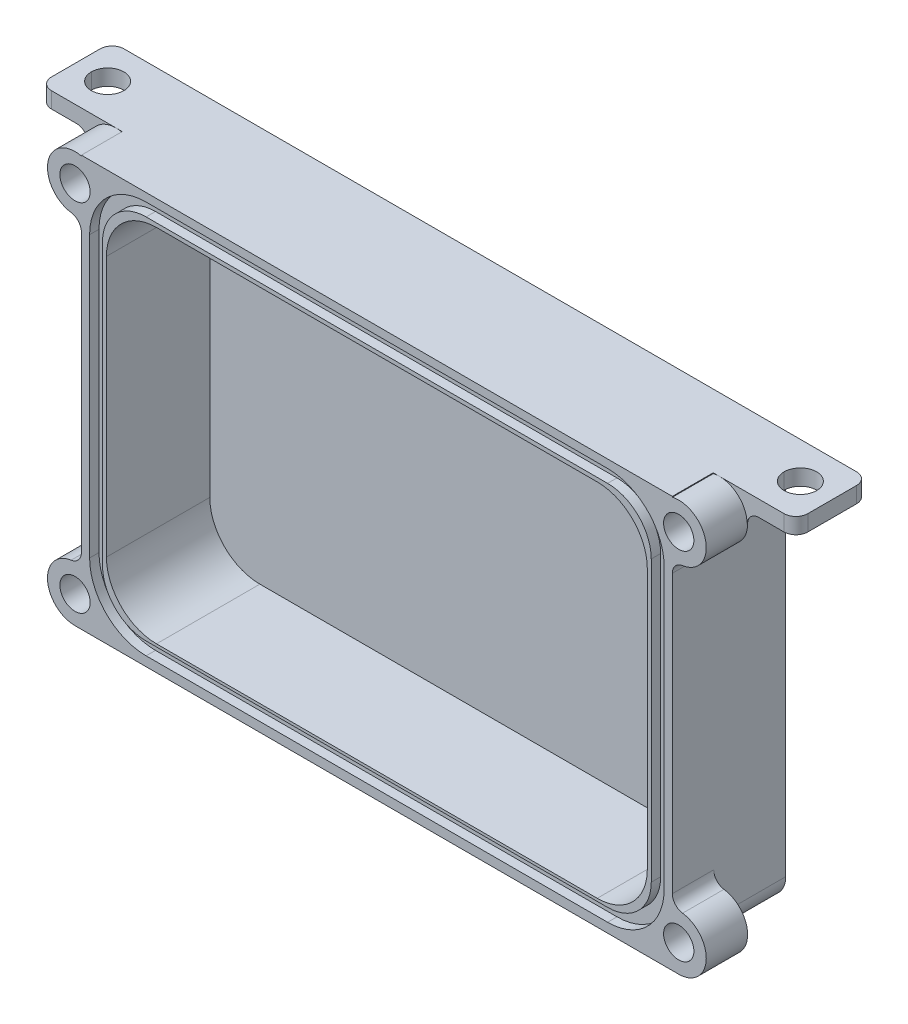
SolidWorks part; units mm, degrees
note: The reader was unsure of these and kept them because the rebuilt part matched: shared geometry of "Sketch6<4>".
material "ABS PC"
ref_plane "X-Y Datum" through (0, 0, 0) normal (0, 0, 1) x (1, 0, 0)
ref_plane "X-Z Datum" through (0, 0, 0) normal (0, 1, 0) x (1, 0, 0)
ref_plane "Y-Z Datum" through (0, 0, 0) normal (1, 0, 0) x (0, 0, -1)
sketch "Sketch2" plane through (0, 0, 0) normal (0, 0, 1) x (1, 0, 0)
  line L1 (-54, 36) -> (54, 36)
  line L2 (-54, 36) -> (-54, -36)
  line L3 (-54, -36) -> (54, -36)
  line L4 (54, 36) -> (54, -36)
  line L5 (-54, 36) -> (54, -36) construction
  line L6 (-54, -36) -> (54, 36) construction
  point P0 (0, 0)
  dimension "D1" = 72
  dimension "D2" = 108
extrude "Boss-Extrude1" add sketch "Sketch2" along normal blind 20.64
shell "Shell1" thickness 5
sketch "Sketch3" plane through (0, 0, -5) normal (0, 0, -1) x (-1, 0, 0)
  line L4 (59, 41) -> (-59, 41)
  line L5 (-59, 41) -> (-59, -41)
  line L6 (-59, -41) -> (59, -41)
  line L7 (59, -41) -> (59, 41)
  line L8 (59, 41) -> (-59, 41)
  line L9 (-59, 41) -> (-59, -41)
  line L10 (-59, -41) -> (59, -41)
  line L11 (59, -41) -> (59, 41)
  dimension "D1" = 0
extrude "Cut-Extrude1" cut sketch "Sketch3" against normal blind 3
fillet "Fillet1" radius 10 4 edges at (54, -36, 10.32) (-54, -36, 10.32) (54, 36, 10.32) (-54, 36, 10.32)
sketch "Sketch13" plane through (0, 41, 0) normal (0, 1, 0) x (1, 0, 0)
  line L1 (-59, 2) -> (-75.51, 2)
  line L2 (-59, 2) -> (-59, -12.478)
  line L3 (-59, -12.478) -> (-75.51, -12.478)
  line L4 (-75.51, 2) -> (-75.51, -12.478)
  line L5 (-59, 2) -> (59, 2) construction
  line L6 (-75.51, -5.239) -> (-59, -5.239) construction
  line L7 (-59, -20.64) -> (-59, 2) construction
  circle A0 centre (-69.16, -5.239) radius 3.25
  point P8 (-63.0691, -9.32)
  point P13 (-67.383, -9.32)
  point P16 (-70.43, -4.0285)
  dimension "D1" = 6.5
  dimension "D2" = 10.16
  dimension "D3" = 16.51
  dimension "D4" = 7.239
  dimension "D5" = 14.478
extrude "Boss-Extrude4" add sketch "Sketch13" against normal blind 3.175 contours A0 | L1 L4 L3 L2
mirror "Mirror4" about plane through (0, 0, 0) normal (1, 0, 0) of "Boss-Extrude4"
sketch "Sketch6" plane through (0, 0, 20.64) normal (0, 0, 1) x (1, 0, 0)
  line L0 (-59, -41) -> (59, -41) construction
  line L1 (60.27, -41) -> (59, -41)
  line L3 (12.452, 0) -> (-12.452, 0) construction
  line L6 (0, -12.452) -> (0, 12.452) construction
  line L7 (59, -41) -> (59, 41) construction
  line L8 (59, -41) -> (59, -40.8514)
  arc A2 (60.27, -41) -> (59, -40.8514) centre (60.27, -35.5) ccw
  circle A3 centre (60.27, -35.5) radius 3.025
  circle A6 centre (60.27, 35.5) radius 5.5
  circle A7 centre (60.27, 35.5) radius 3.025
  circle A8 centre (-60.27, -35.5) radius 3.025
  circle A9 centre (-60.27, -35.5) radius 5.5
  circle A10 centre (-60.27, 35.5) radius 3.025
  circle A11 centre (-60.27, 35.5) radius 5.5
  line M16 (59, -41) -> (59, 41)
  line M20 (-59, 41) -> (-59, -41)
  dimension "D1" = 11
  dimension "D2" = 6.05
  dimension "D3" = 1.27
extrude "Boss-Extrude2" add sketch "Sketch6" against normal blind 8.255
extrude "Cut-Extrude4" cut sketch "Sketch6<4>" against normal blind 6.35 contours A7 M16 | A7 M16 | A3 M16 | A3 M16 | A8 M20 | A8 M20 | A10 M20 | A10 M20
sketch "Sketch6<4>" plane through (0, 0, 20.64) normal (0, 0, 1) x (1, 0, 0) same geometry as "Sketch6"
mirror "Mirror5" about plane through (0, 0, 0) normal (1, 0, 0) of "Cut-Extrude4", "Boss-Extrude2"
sketch "Sketch5" plane through (0, 0, 20.64) normal (0, 0, 1) x (1, 0, 0)
  line L0 (-46.0711, 38.0711) -> (46.0711, 38.0711) construction
  line L5 (56.0711, 28.0711) -> (56.0711, -27.825) construction
  line L6 (46.0711, -37.825) -> (-46.0711, -37.825) construction
  line L7 (-56.0711, -27.825) -> (-56.0711, 28.0711) construction
  line L8 (46.0711, -39.11) -> (-46.0711, -39.11)
  line L9 (-57.3561, -27.825) -> (-57.3561, 28.0711)
  line L10 (-46.0711, 39.3561) -> (46.0711, 39.3561)
  line L11 (57.3561, 28.0711) -> (57.3561, -27.825)
  line L12 (46.0711, -36.54) -> (-46.0711, -36.54)
  line L13 (-54.7861, -27.825) -> (-54.7861, 28.0711)
  line L14 (-46.0711, 36.7861) -> (46.0711, 36.7861)
  line L15 (54.7861, 28.0711) -> (54.7861, -27.825)
  line L16 (-44, -36) -> (44, -36) construction
  arc A0 (-49, 41) -> (-59, 31) centre (-49, 31) ccw construction
  arc A1 (59, 31) -> (49, 41) centre (49, 31) ccw construction
  arc A2 (56.0711, -27.825) -> (46.0711, -37.825) centre (46.0711, -27.825) cw construction
  arc A3 (46.0711, 38.0711) -> (56.0711, 28.0711) centre (46.0711, 28.0711) cw construction
  arc A4 (-46.0711, 38.0711) -> (-56.0711, 28.0711) centre (-46.0711, 28.0711) ccw construction
  arc A5 (-46.0711, -37.825) -> (-56.0711, -27.825) centre (-46.0711, -27.825) cw construction
  arc A6 (-46.0711, -39.11) -> (-57.3561, -27.825) centre (-46.0711, -27.825) cw
  arc A7 (-46.0711, 39.3561) -> (-57.3561, 28.0711) centre (-46.0711, 28.0711) ccw
  arc A8 (46.0711, 39.3561) -> (57.3561, 28.0711) centre (46.0711, 28.0711) cw
  arc A9 (57.3561, -27.825) -> (46.0711, -39.11) centre (46.0711, -27.825) cw
  arc A10 (-46.0711, -36.54) -> (-54.7861, -27.825) centre (-46.0711, -27.825) cw
  arc A11 (-46.0711, 36.7861) -> (-54.7861, 28.0711) centre (-46.0711, 28.0711) ccw
  arc A12 (46.0711, 36.7861) -> (54.7861, 28.0711) centre (46.0711, 28.0711) cw
  arc A13 (54.7861, -27.825) -> (46.0711, -36.54) centre (46.0711, -27.825) cw
  point P18 (56.0711, 38.0711)
  point P21 (-56.0711, 38.0711)
  dimension "D1" = 10
  dimension "D4" = 1.825
  dimension "D2" = 1.285
  dimension "D3" = 1.285
extrude "Cut-Extrude2" cut sketch "Sketch5" against normal blind 1.875
fillet "Fillet2" [suppressed] radius 15.08
fillet "Fillet3" radius 2.38 6 edges at (59, 30.1486, 16.5125) (65.2544, 37.825, 12.4315) (59, -30.1486, 16.5125) (-59, -30.1486, 16.5125) (-65.2544, 37.825, 12.4315) (-59, 30.1486, 16.5125)
fillet "Fillet4" radius 4.92 4 edges at (59, -41, 5.1925) (59, 37.825, 5.1925) (-59, 37.825, 5.1925) (-59, -41, 5.1925)
fillet "Fillet5" radius 2.38 4 edges at (75.51, 39.4125, -2) (75.51, 39.4125, 12.478) (-75.51, 39.4125, 12.478) (-75.51, 39.4125, -2)
